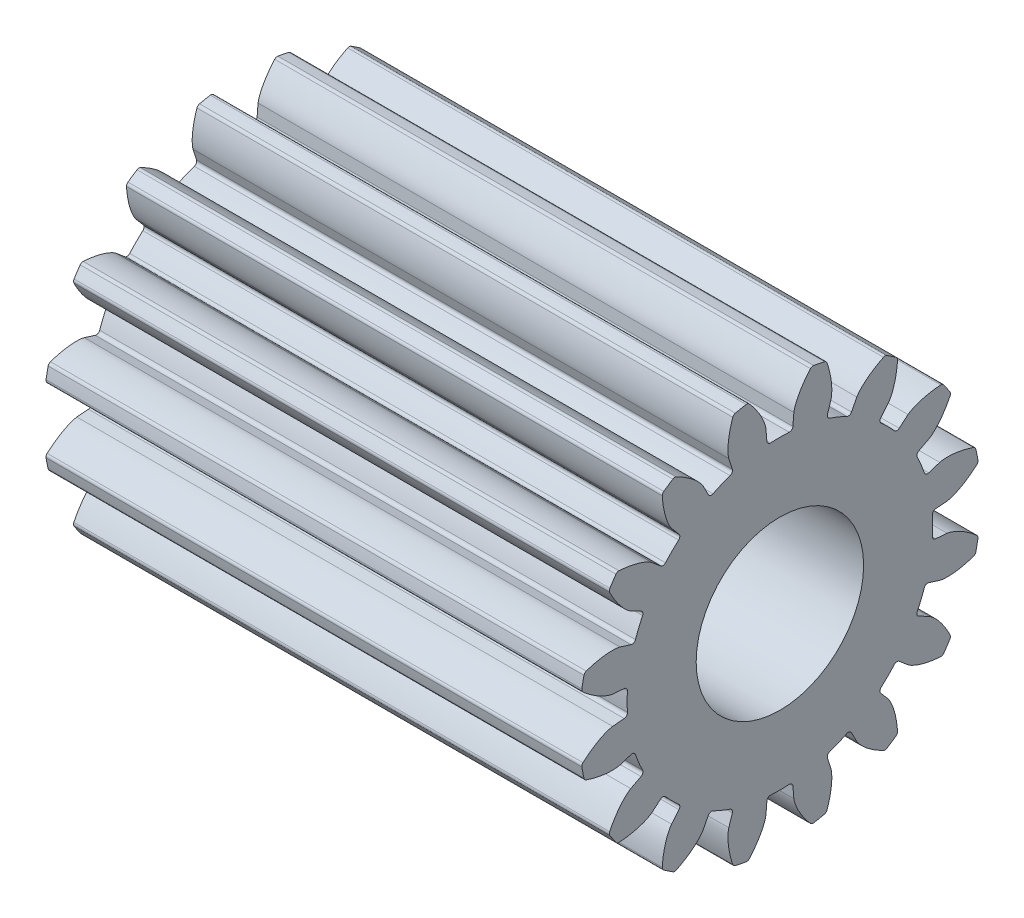
SolidWorks part; units mm, degrees
ref_plane "Front Plane" through (0, 0, 0) normal (1, 0, 0) x (0, 1, 0)
ref_plane "Top Plane" through (0, 0, 0) normal (0, 0, 1) x (0, 1, 0)
ref_plane "Right Plane" through (0, 0, 0) normal (0, 1, 0) x (-1, 0, 0)
sketch "Sketch2" plane through (0, 0, 0) normal (1, 0, 0) x (0, 1, 0)
  circle A0 centre (0, 0) radius 3.9688
  circle A1 centre (0, 0) radius 9.525
  dimension "D1" = 7.9375
  dimension "D2" = 19.05
extrude "Gear Width Extrude" add sketch "Sketch2" along normal blind 25.4
sketch "Sketch3" plane through (0, 0, 0) normal (1, 0, 0) x (0, 1, 0)
  line L0 (-9.525, 0) -> (9.525, 0) construction
  line L1 (0, 9.525) -> (0, -9.525) construction
  line L2 (0, 0) -> (7.9285, 0.6617) construction
  line L5 (7.2422, 0) -> (9.525, 0)
  line L6 (7.9285, 0.6617) -> (7.2171, 0.6024)
  circle A0 centre (0, 0) radius 7.2422 construction
  circle A1 centre (0, 0) radius 7.9561 construction
  circle A2 centre (0, 0) radius 8.4667 construction
  circle A3 centre (0, 0) radius 9.525 construction
  arc A7 (9.4043, 1.5115) -> (9.525, 0) centre (0, 0) cw
  arc A8 (7.2171, 0.6024) -> (7.2422, 0) centre (0, 0) cw
  spline S0 degree 4 poles (7.9285, 0.6617) (7.931, 0.662) (7.9381, 0.6628) (7.96, 0.666) (8.0029, 0.6742) (8.0554, 0.6873) (8.1153, 0.705) (8.1727, 0.7241) (8.2215, 0.7418) (8.2698, 0.7607) (8.3177, 0.7806) (8.3754, 0.8059) (8.4441, 0.8381) (8.5236, 0.8782) (8.6129, 0.9268) (8.7028, 0.9795) (8.7904, 1.0339) (8.8778, 1.0919) (8.9615, 1.1501) (9.0473, 1.2136) (9.1259, 1.2737) (9.2126, 1.3443) (9.2821, 1.4022) (9.3723, 1.4821) (9.425, 1.5303) (9.4863, 1.5879) (9.5131, 1.6141) (9.5297, 1.6302) knots 0 0 0 0 0 0.005377 0.015084 0.04661 0.092111 0.119476 0.146842 0.174209 0.201575 0.228941 0.256307 0.307035 0.361767 0.4165 0.471232 0.525964 0.580697 0.635429 0.690161 0.744894 0.799626 0.854358 0.909091 0.954545 1 1 1 1 1 construction
  spline S1 degree 4 poles (7.9285, 0.6617) (7.931, 0.662) (7.9381, 0.6628) (7.96, 0.666) (8.0029, 0.6742) (8.0554, 0.6873) (8.1153, 0.705) (8.1727, 0.7241) (8.2215, 0.7418) (8.2698, 0.7607) (8.3177, 0.7806) (8.3754, 0.8059) (8.4441, 0.8381) (8.5236, 0.8782) (8.6129, 0.9268) (8.7028, 0.9795) (8.7904, 1.0339) (8.8778, 1.0919) (8.9615, 1.1501) (9.0473, 1.2136) (9.1259, 1.2737) (9.2126, 1.3443) (9.2821, 1.4022) (9.3527, 1.4648) (9.3869, 1.4956) (9.4043, 1.5115) knots 0 0 0 0 0 0.005377 0.015084 0.04661 0.092111 0.119476 0.146842 0.174209 0.201575 0.228941 0.256307 0.307035 0.361767 0.4165 0.471232 0.525964 0.580697 0.635429 0.690161 0.744894 0.799626 0.854358 0.909091 0.909091 0.909091 0.909091 0.909091
  dimension "D1" = 16.9333
  dimension "D2" = 15.9121
  dimension "D3" = 14.4843
extrude "Gear Tooth Cut" cut sketch "Sketch3" along normal blind 25.4 contours S1 region at (0, 8.5569, 0.4875)
mirror "Gear Tooth Cut Mirror" about plane through (25.4, 0, 0) normal (0, 0, 1) of "Gear Tooth Cut"
fillet "Tooth Fillets" radius 0.1662 4 edges at (12.7, 9.4043, 1.5115) (12.7, 9.4043, -1.5115) (12.7, 7.2171, 0.6024) (12.7, 7.2171, -0.6024)
pattern_circular "CirPattern1" count 16 over 360 about axis through (0, 0, 0) along (1, 0, 0) of "Gear Tooth Cut", "Gear Tooth Cut Mirror", "Tooth Fillets"
equation "\"DP\" = 24'INPUT: Diametral Pitch"
equation "\"a_Pressure\"= 20'INPUT: Pressure Angle"
equation "\"Z\" = 16'INPUT: Number of Teeth"
equation "\"w_Face\"= 1'INPUT: Face Width"
equation "\"d_Bore\"= 5 / 16'INPUT: Bore Diameter"
equation "\"d_Pitch\"= \"Z\" / \"DP\"'Pitch Diameter"
equation "\"Module\"= 1 / \"DP\"'Module"
equation "\"d_Base\"= \"d_Pitch\" * cos ( \"a_Pressure\" )'Base Circle Diameter"
equation "\"Clearance\"= 0.157 / \"DP\"'Clearance"
equation "\"CP\"= pi * \"d_Pitch\" / \"Z\"'Circular Pitch"
equation "\"h_Addendum\"= 1 / \"DP\"'Addendum Depth"
equation "\"h_Dedendum\" = IIF ( \"h_deStandard\" > \"h_deMin\" , \"h_deStandard\" , \"h_deMin\" )'Dedendum Depth"
equation "\"d_Addendum\"= \"d_Pitch\" + ( 2 * \"h_Addendum\" )'Addendum (Tip) Diameter"
equation "\"d_Dedendum\"= \"d_Pitch\" - ( 2 * \"h_Dedendum\" )'Dedendum (Root) Diameter"
equation "\"a_Pitch\"= 360 / \"Z\"'Pitch Angle"
equation "\"a_Alpha\"= ( ( 180 * ( ( \"d_Pitch\" ^ 2 ) - ( \"d_Base\" ^ 2 ) ) ^ 0.5 ) / ( pi * \"d_Base\" ) ) - \"a_Pressure\"'Alpha Angle"
equation "\"a_Beta\"= ( \"a_Pitch\" / 4 ) - \"a_Alpha\"'Beta Angle"
equation "\"ICDP\"= ( ( ( \"d_Addendum\" / 2 ) ^ 2 - ( \"d_Base\" / 2 ) ^ 2 ) ^ 0.5 ) * ( 2 / \"d_Base\" )'Involute Curve Domain Parameter"
equation "\"D1@Sketch2\"=\"d_Bore\""
equation "\"D2@Sketch2\"=\"d_Addendum\""
equation "\"D1@Gear Width Extrude\" = \"w_Face\""
equation "\"D1@Sketch3\"=\"d_Pitch\""
equation "\"D2@Sketch3\"=\"d_Base\""
equation "\"D3@Sketch3\"= \"d_Dedendum\""
equation "\"D1@CirPattern1\"=\"Z\""
equation "\"D1@Tooth Fillets\"=\"Clearance\""
equation "\"h_deStandard\"= ( 1 / \"DP\" ) + \"Clearance\""
equation "\"h_deMin\"= ( \"d_Pitch\" * ( 1 - cos ( \"a_Pressure\" ) ) / 2 ) + \"Clearance\""
